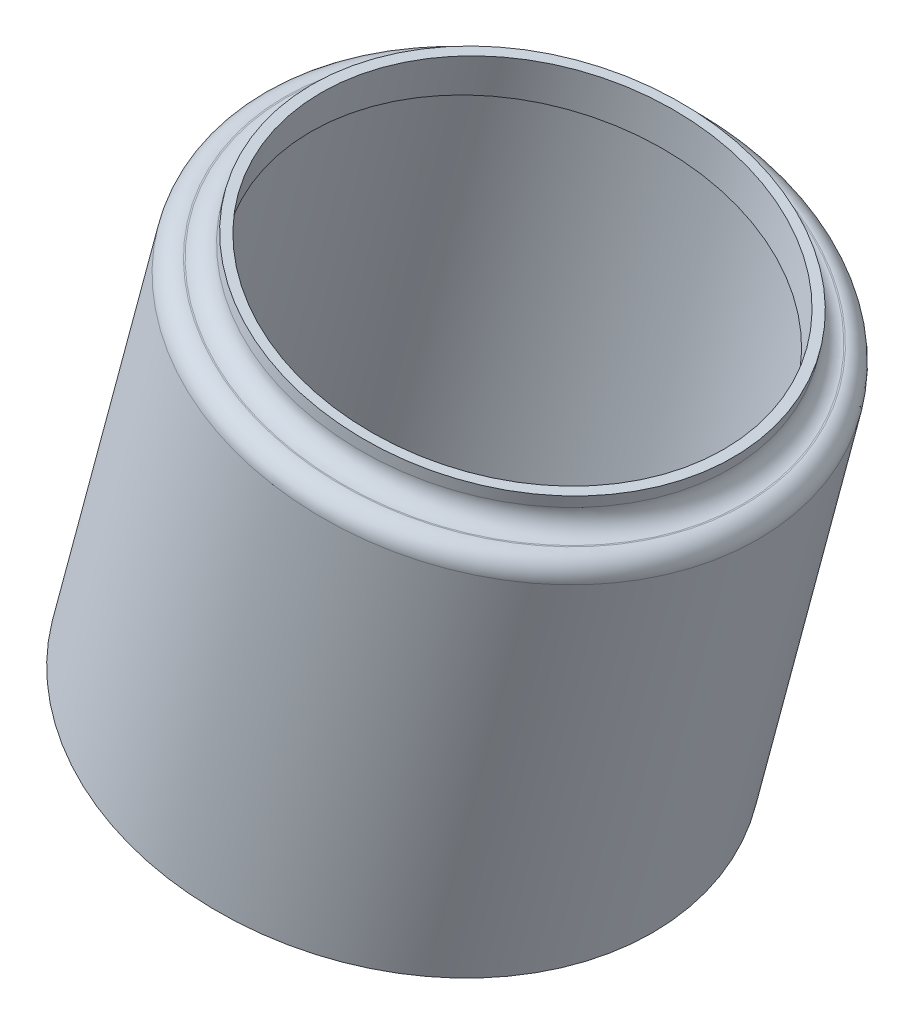
SolidWorks part; units mm, degrees
material "Polyethylene Cross-Linked"
ref_plane "Front Plane" through (0, 0, 0) normal (0, 0, 1) x (1, 0, 0)
ref_plane "Top Plane" through (0, 0, 0) normal (0, 1, 0) x (1, 0, 0)
ref_plane "Right Plane" through (0, 0, 0) normal (1, 0, 0) x (0, 0, -1)
sketch "Sketch1" plane through (0, 0, 0) normal (0, 0, 1) x (1, 0, 0)
  line L0 (111.0781, -7.7629) -> (107.7911, -20.0301) construction
  line L2 (114.1701, -21.7394) -> (117.0462, -11.0055)
  line L4 (117.0462, -11.0055) -> (116.0342, -10.7344)
  line L7 (116.0342, -10.7344) -> (116.3136, -9.6916)
  line L8 (114.4155, -21.8051) -> (117.2259, -11.3166)
  line L9 (116.8666, -10.6944) -> (116.836, -10.6862)
  line L10 (116.4768, -10.0641) -> (116.5589, -9.7574)
  line L11 (114.1701, -21.7394) -> (114.4155, -21.8051)
  line L12 (116.3136, -9.6916) -> (116.5589, -9.7574)
  line L13 (117.3573, -10.8259) -> (116.3453, -10.5547) construction
  line L14 (116.3453, -10.5547) -> (116.5589, -9.7574) construction
  line L15 (114.4155, -21.8051) -> (117.3573, -10.8259) construction
  arc A0 (116.836, -10.6862) -> (116.4768, -10.0641) centre (116.9675, -10.1955) cw
  arc A1 (117.2259, -11.3166) -> (116.8666, -10.6944) centre (116.7352, -11.1851) ccw
  dimension "D3" = 0.508
  dimension "D4" = 0.508
  dimension "D1" = 12.7
  dimension "D2" = 0.254
revolve "Revolve1" add sketch "Sketch1" angle 360 about L0
